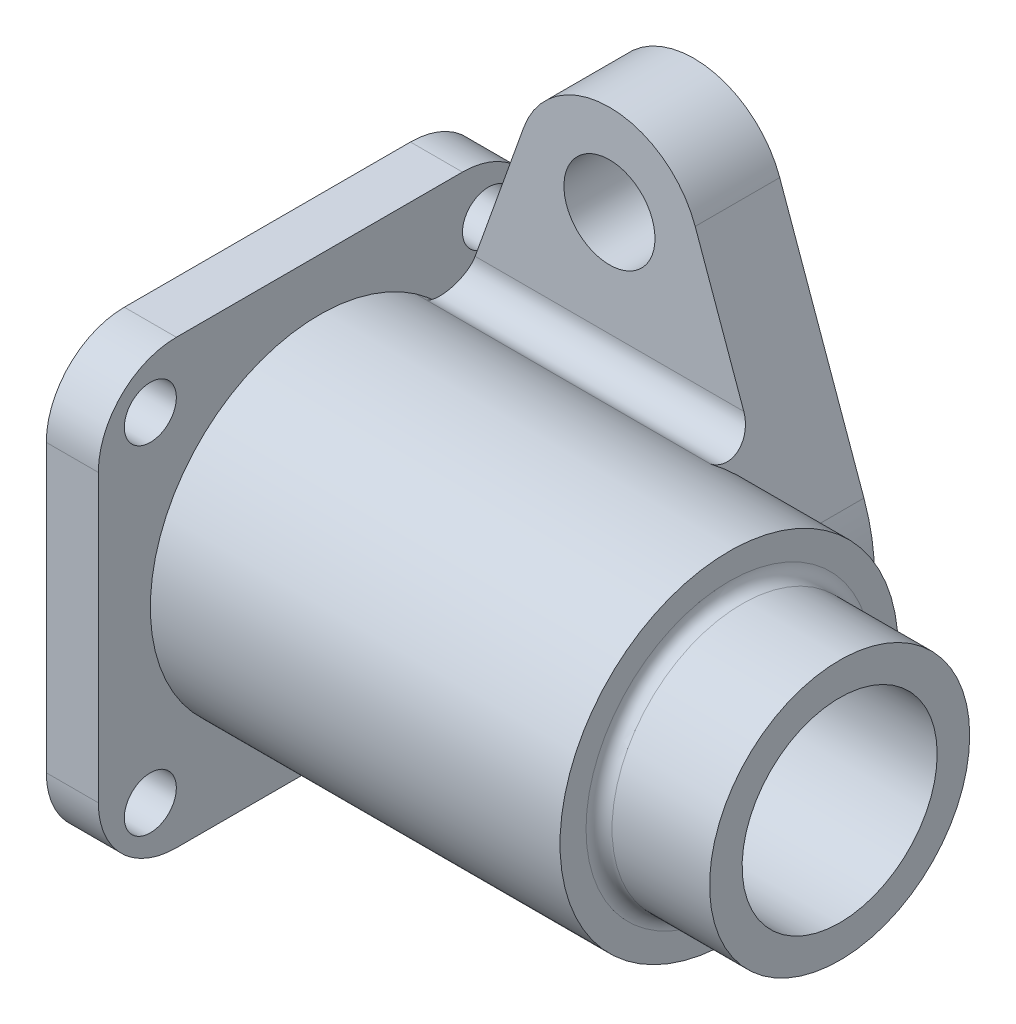
SolidWorks part; units mm, degrees
ref_plane "Front Plane" through (0, 0, 0) normal (0, 0, 1) x (1, 0, 0)
ref_plane "Top Plane" through (0, 0, 0) normal (0, 1, 0) x (1, 0, 0)
ref_plane "Right Plane" through (0, 0, 0) normal (1, 0, 0) x (0, 0, -1)
sketch "Sketch1" plane through (0, 0, 0) normal (0, 0, 1) x (1, 0, 0)
  line L0 (0, 253.7592) -> (0, 27.75) construction
  line L1 (-302.3192, 0) -> (365.0346, 0) construction
  line L2 (-13.1826, 45.5519) -> (-26.1298, 9.3433)
  line L3 (13.1826, 45.5519) -> (26.1298, 9.3433)
  line L4 (-25.9833, -9.7432) -> (-13.1087, -44.0774)
  line L5 (13.1087, -44.0774) -> (25.9833, -9.7432)
  line L6 (0, 26.8381) -> (0, -332.083) construction
  circle A1 centre (0, 40.8381) radius 7
  circle A2 centre (0, -39.1619) radius 7
  arc A3 (13.1826, 45.5519) -> (-13.1826, 45.5519) centre (0, 40.8381) ccw
  arc A6 (-13.1087, -44.0774) -> (13.1087, -44.0774) centre (0, -39.1619) ccw
  arc A7 (-26.1298, 9.3433) -> (-25.9833, -9.7432) centre (0, 0) ccw
  arc A8 (25.9833, -9.7432) -> (26.1298, 9.3433) centre (0, 0) ccw
  circle A9 centre (0, 0) radius 15
  point P20 (0, 0)
  point P21 (0, 0)
  point P22 (0, 0)
  point P23 (0, 0)
  dimension "D1" = 30
  dimension "D2" = 14
  dimension "D3" = 14
  dimension "D4" = 28
  dimension "D5" = 27.75
  dimension "D6" = 80
extrude "Boss-Extrude1" add sketch "Sketch1" against normal blind 13
ref_plane "Plane2" through (-27.5, 0, 0) normal (1, 0, 0) x (0, 0, -1)
sketch "Sketch2" plane through (-27.5, 0, 0) normal (1, 0, 0) x (0, 0, -1)
  line L0 (56.078, 0) -> (-55.1033, 0) construction
  line L1 (-21.1033, 53.0366) -> (-21.1033, -66.5825) construction
  line L2 (-43.1033, 34) -> (0.8967, 34)
  line L3 (-55.1033, 22) -> (-55.1033, -22)
  line L4 (-43.1033, -34) -> (0.8967, -34)
  line L5 (12.8967, 22) -> (12.8967, -22)
  line L6 (-47.1033, 26) -> (27.4922, 26) construction
  line L7 (-47.1033, -26) -> (27.4922, -26) construction
  line L8 (-47.1033, -26) -> (-47.1033, 60.691) construction
  line L9 (4.8967, -26) -> (4.8967, 39.4787) construction
  circle A0 centre (-47.1033, 26) radius 4
  circle A1 centre (-47.1033, -26) radius 4
  circle A2 centre (4.8967, 26) radius 4
  circle A3 centre (4.8967, -26) radius 4
  arc A8 (0.8967, -34) -> (12.8967, -22) centre (0.8967, -22) ccw
  arc A9 (12.8967, 22) -> (0.8967, 34) centre (0.8967, 22) ccw
  arc A10 (-43.1033, -34) -> (-55.1033, -22) centre (-43.1033, -22) cw
  arc A11 (-43.1033, 34) -> (-55.1033, 22) centre (-43.1033, 22) ccw
  point P20 (12.8967, -34)
  point P30 (-55.1033, -34)
  point P33 (-55.1033, 34)
  dimension "D4" = 8
  dimension "D5" = 12
  dimension "D1" = 68
  dimension "D2" = 68
  dimension "D3" = 52
  dimension "D6" = 52
  dimension "D7" = 34
extrude "Boss-Extrude2" add sketch "Sketch2" along normal mid plane 8 separate body
sketch "Sketch5" plane through (-23.5, 0, 0) normal (1, 0, 0) x (0, 0, -1)
  line L0 (-79.5358, 0) -> (44.9849, 0) construction
  line L1 (-21.1033, 34) -> (-21.1033, -49.3552) construction
  line L2 (0.8967, 34) -> (-43.1033, 34) construction
  circle A0 centre (-21.1033, 0) radius 26
  point P9 (-21.1033, 0)
  point P10 (0, 0)
  point P11 (-21.1033, 0)
  dimension "D1" = 52
extrude "Boss-Extrude3" add sketch "Sketch5" along normal blind 63
fillet "Fillet6" radius 4 1 edges at (0.221, -15.1872, 0) type face fillet first side face at (9.0921, 0.4734, 6.492) second side face at (-4.6116, -28.7959, 0)
fillet "Fillet7" radius 4 1 edges at (0.2701, 15.1872, 0) type face fillet first side face at (4.3517, -3.6172, 7.2986) second side face at (-4.592, 29.4925, 0)
sketch "Sketch6" plane through (-31.5, 0, 0) normal (-1, 0, 0) x (0, 0, 1)
  circle A0 centre (21.1033, 0) radius 21
  dimension "D1" = 42
extrude "Cut-Extrude1" cut sketch "Sketch6" against normal blind 22
sketch "Sketch7" plane through (-9.5, 0, 0) normal (-1, 0, 0) x (0, 0, 1)
  circle A0 centre (21.1033, 0) radius 15
  dimension "D1" = 30
extrude "Cut-Extrude2" cut sketch "Sketch7" against normal up to next
sketch "Sketch9" plane through (39.5, 0, 0) normal (1, 0, 0) x (0, 0, -1)
  circle A0 centre (-21.1033, 0) radius 15
  dimension "D1" = 30
extrude "Boss-Extrude4" add sketch "Sketch9" against normal blind 43
fillet "Fillet10" radius 2 1 edges at (-31.5, 0, 42.1033)
sketch "Sketch12" plane through (39.5, 0, 0) normal (1, 0, 0) x (0, 0, -1)
  circle A0 centre (-21.1033, 0) radius 20
  dimension "D1" = 40
extrude "Boss-Extrude5" add sketch "Sketch12" along normal blind 17
fillet "Fillet14" radius 2 1 edges at (39.5, 0, 1.1033) type face fillet first side face at (56.5, 0, 1.1033) second side face at (39.5, 0, 1.1033)
sketch "Sketch16" plane through (56.5, 0, 0) normal (1, 0, 0) x (0, 0, -1)
  circle A0 centre (-21.1033, 0) radius 15
  dimension "D1" = 30
extrude "Cut-Extrude4" cut sketch "Sketch16" against normal up to next
sketch "Sketch17" plane through (0, 0, -13) normal (0, 0, -1) x (-1, 0, 0)
  circle A0 centre (0, 0) radius 15
extrude "Cut-Extrude5" cut sketch "Sketch17" against normal up to next
fillet "Fillet17" radius 5 1 edges at (15, 0, -13) type face fillet first side face at (15, 0, -13) second side face at (15, 0, -13)
sketch "Sketch15" plane through (56.5, 0, 0) normal (1, 0, 0) x (0, 0, -1)
  circle A0 centre (-21.1033, 0) radius 15
